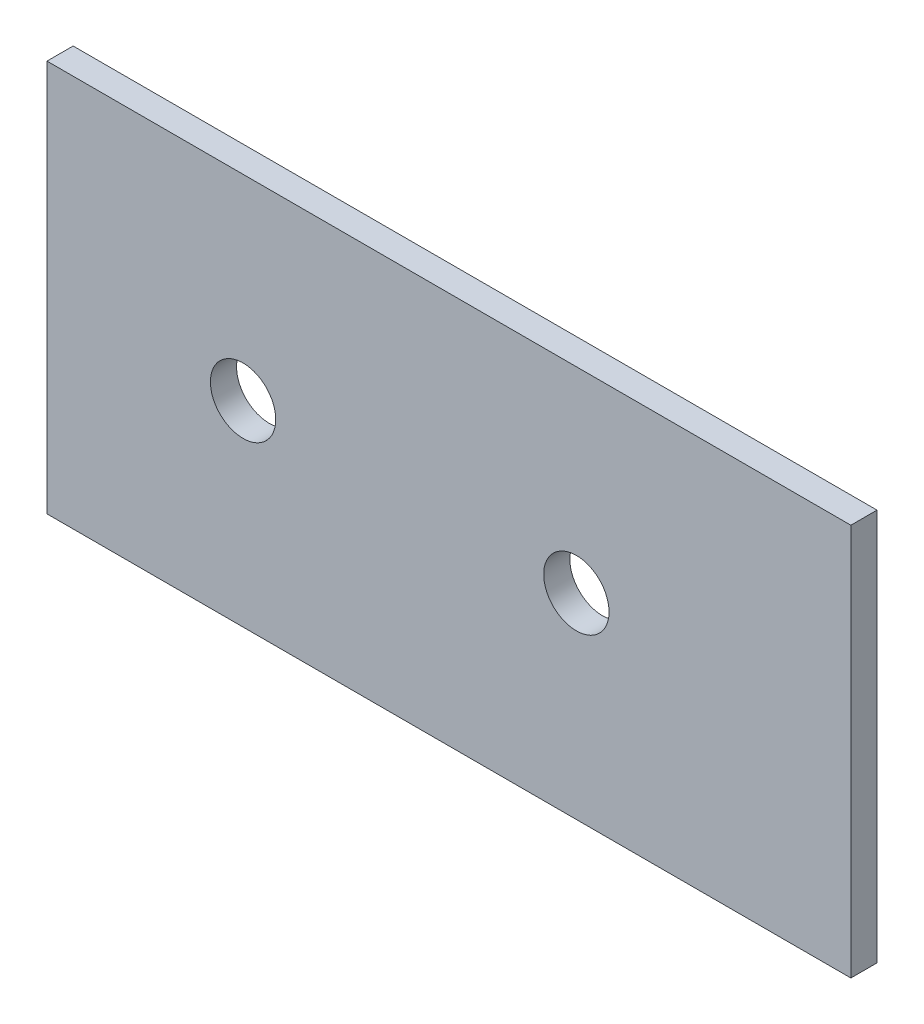
SolidWorks part; units mm, degrees
ref_plane "Front Plane" through (0, 0, 0) normal (0, 0, 1) x (1, 0, 0)
ref_plane "Top Plane" through (0, 0, 0) normal (0, 1, 0) x (1, 0, 0)
ref_plane "Right Plane" through (0, 0, 0) normal (1, 0, 0) x (0, 0, -1)
sketch "Sketch1" plane through (0, 0, 0) normal (0, 0, 1) x (1, 0, 0)
  line L1 (-81, -30) -> (42, -30)
  line L2 (-81, -30) -> (-81, 30)
  line L3 (-81, 30) -> (42, 30)
  line L4 (42, -30) -> (42, 30)
  circle A0 centre (0, 0) radius 5
  circle A2 centre (-51, 0) radius 5
  point P1 (0, 0)
  point P8 (-81, 0)
  dimension "D3" = 10
  dimension "D4" = 0
  dimension "D5" = 30
  dimension "D2" = 60
  dimension "D8" = 51
  dimension "D9" = 42
extrude "Boss-Extrude1" add sketch "Sketch1" along normal blind 4
